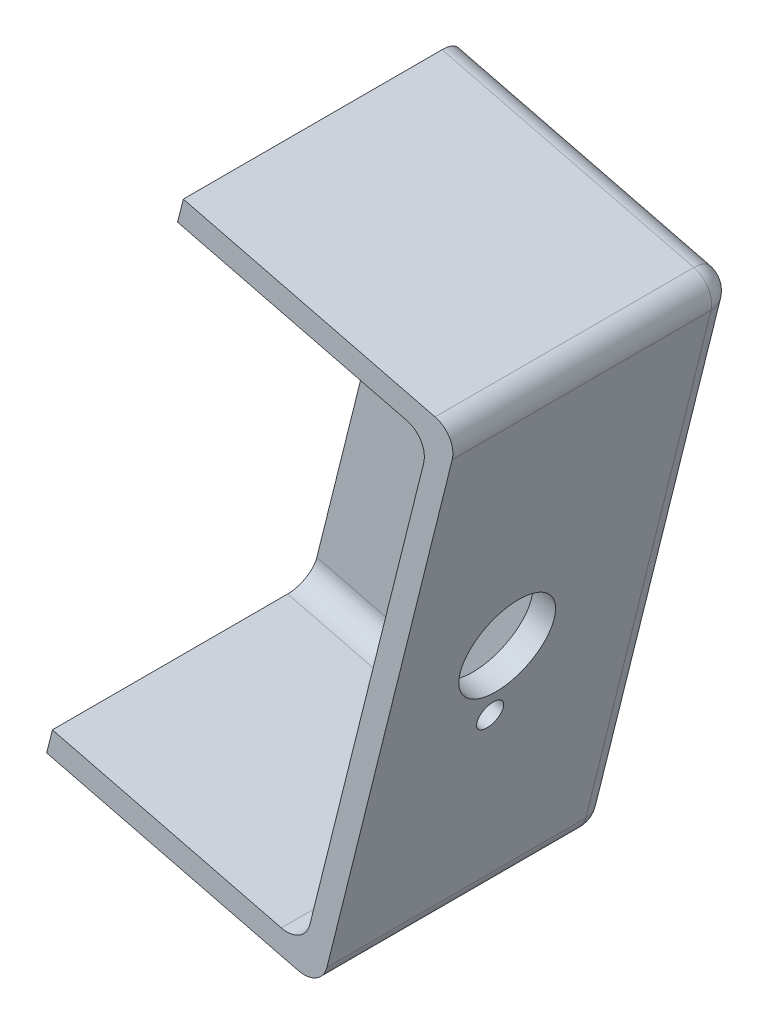
SolidWorks part; units mm, degrees
material "PET"
ref_plane "Front" through (0, 0, 0) normal (0, 0, 1) x (1, 0, 0)
ref_plane "Top" through (0, 0, 0) normal (0, 1, 0) x (1, 0, 0)
ref_plane "Right" through (0, 0, 0) normal (1, 0, 0) x (0, 0, -1)
sketch "Sketch1" plane through (0, 0, 0) normal (0, 0, 1) x (1, 0, 0)
  line L0 (-450.5686, 3232.3188) -> (-413.5136, 3223.0799)
  line L1 (-413.5136, 3223.0799) -> (-431.9476, 3149.1454)
  line L2 (-431.9476, 3149.1454) -> (-469.003, 3158.3822)
extrude "Extrude-Thin1" add sketch "Sketch1" against normal up to surface (38.1 mm away) thin thin type one direction wall 3.175
sketch "Sketch2" plane through (0, 0, -38.1) normal (0, 0, -1) x (-1, 0, 0)
  line L0 (413.5136, 3223.0799) -> (431.9476, 3149.1454)
  line L1 (413.5136, 3223.0799) -> (431.9476, 3149.1454) construction
  line L2 (431.9476, 3149.1454) -> (469.003, 3158.3822) construction
  line L3 (431.9476, 3149.1454) -> (469.003, 3158.3822)
  line L4 (469.003, 3158.3822) -> (450.5686, 3232.3188)
  line L5 (450.5686, 3232.3188) -> (413.5136, 3223.0799)
extrude "Boss-Extrude1" add sketch "Sketch2" against normal blind 3.175
hole_wizard "#8 Clearance Hole1" positions "Sketch4" profile "Sketch3" hole size "#8" standard "ANSI Inch" end condition through all
sketch "Sketch4" plane through (0, 0, -34.925) normal (0, 0, 1) x (1, 0, 0)
  point P0 (-439.7738, 3209.9941)
  point P2 (-448.991, 3173.0259)
sketch "Sketch3" plane through (-439.7738, 3209.9941, -34.925) normal (1, 0, 0) x (0, -1, 0)
  line L0 (0, 0) -> (0, 3.175)
  line L1 (0, 3.175) -> (2.4574, 3.175)
  line L2 (2.4574, 3.175) -> (2.4574, 0)
  line L5 (2.4574, 0) -> (0, 0)
  line L11 (0, -6.35) -> (0, 107.95) construction
  dimension "Thru Hole Dia." = 4.9149
  dimension "Thru Hole Depth" = 3.175
fillet "Fillet1" radius 3.175 9 edges at (-413.5136, 3223.0799, -19.05) (-417.3624, 3220.7674, -17.4625) (-434.3496, 3225.0027, -34.925) (-451.2476, 3157.2285, -34.925) (-434.2602, 3152.994, -17.4625) (-450.4753, 3153.7638, -38.1) (-431.9476, 3149.1454, -19.05) (-432.0411, 3227.6994, -38.1) (-422.7306, 3186.1127, -38.1)
hole_wizard "1/2 (0.5) Diameter Hole1" positions "Sketch6" profile "Sketch5" hole size "1/2" standard "ANSI Inch" end condition through all
sketch "Sketch6" plane through (-1145.8844, 285.7011, 0) normal (0.9703, -0.2419, 0) x (0, 0, -1)
  point P0 (15.875, 2989.2027)
sketch "Sketch5" plane through (-422.7309, 3186.1117, -15.875) normal (0, 0, 1) x (0.2419, 0.9703, 0)
  line L0 (0, 0) -> (0, 56.0762)
  line L1 (0, 56.0762) -> (6.35, 56.0762)
  line L2 (6.35, 56.0762) -> (6.35, 0)
  line L5 (6.35, 0) -> (0, 0)
  line L11 (0, -6.35) -> (0, 107.95) construction
  dimension "Thru Hole Dia." = 12.7
  dimension "Thru Hole Depth" = 56.0762
hole_wizard "9/64 (0.14063) Diameter Hole1" positions "Sketch8" profile "Sketch7" hole size "9/64" standard "ANSI Inch" end condition through all
sketch "Sketch8" plane through (-1145.8844, 285.7011, 0) normal (0.9703, -0.2419, 0) x (0, 0, -1)
  point P0 (15.875, 2979.6777)
sketch "Sketch7" plane through (-425.0352, 3176.8696, -15.875) normal (0, 0, 1) x (0.2419, 0.9703, 0)
  line L0 (0, 0) -> (0, 56.0762)
  line L1 (0, 56.0762) -> (1.786, 56.0762)
  line L2 (1.786, 56.0762) -> (1.786, 0)
  line L5 (1.786, 0) -> (0, 0)
  line L11 (0, -6.35) -> (0, 107.95) construction
  dimension "Thru Hole Dia." = 3.572
  dimension "Thru Hole Depth" = 56.0762
